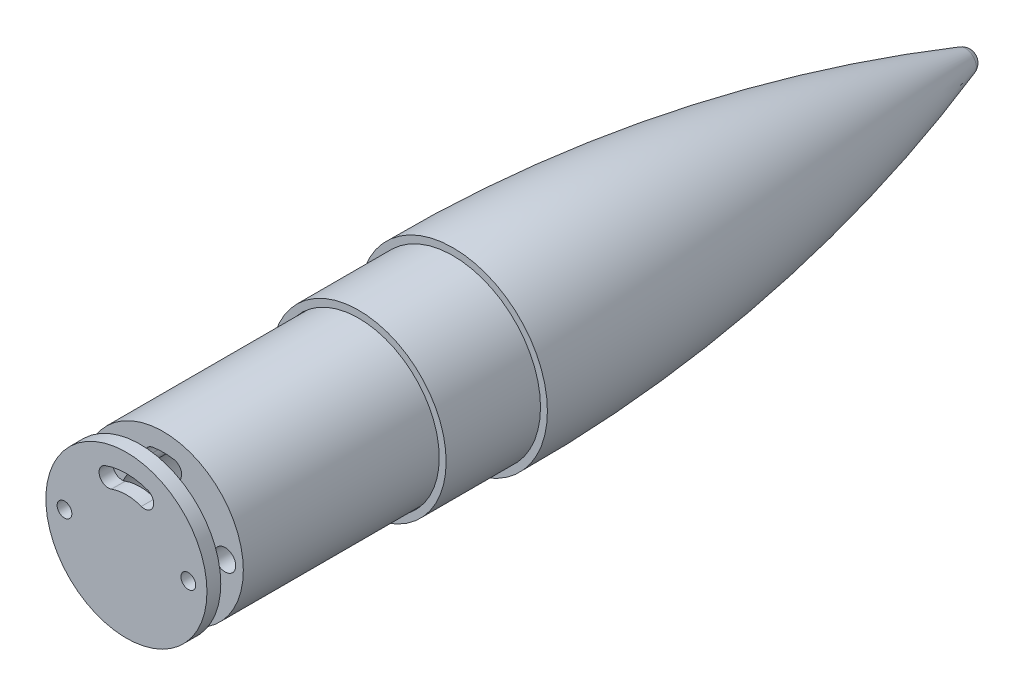
SolidWorks part; units mm, degrees
other "Battery Cover"
other "Battery Bay"
other "Nose Cone"
ref_plane "Front Plane" through (0, 0, 0) normal (0, 0, 1) x (1, 0, 0)
ref_plane "Top Plane" through (0, 0, 0) normal (0, 1, 0) x (1, 0, 0)
ref_plane "Right Plane" through (0, 0, 0) normal (1, 0, 0) x (0, 0, -1)
sketch "Sketch1" plane through (0, 0, 0) normal (0, 1, 0) x (1, 0, 0)
  line L0 (0, 0) -> (0, 110) construction
  line L1 (0, 0) -> (19, 0) construction
  line L2 (19, 0) -> (19, -100) construction
  line L3 (0, 110) -> (-1.2375, 110) construction
  line L4 (19, 0) -> (17.5, 0)
  line L5 (17.5, 0) -> (17.5, -22)
  arc A0 (0, 110) -> (0.9469, 109.3215) centre (0, 109) cw
  arc A1 (0.9469, 109.3215) -> (19, 0) centre (-321.0278, 0) cw
  dimension "D1" = 1
  dimension "D2" = 19
  dimension "D3" = 110
  dimension "D4" = 100
  dimension "D5" = 1.5
  dimension "D7" = 22
revolve "Revolve-Thin1" add sketch "Sketch1" angle 360 about L0 wall 1.5
sketch "Sketch2" plane through (0, 0, 0) normal (0, 1, 0) x (1, 0, 0)
  line L8 (0, 0) -> (0, 45.5852) construction
  line L9 (-17.5, -22) -> (-17.5, 0)
  line L10 (17.5, 0) -> (17.5, -22)
  line L11 (17.5, 0) -> (17.5, -22)
  line L12 (0, 70.542) -> (9.5, 70.542)
  line L13 (9.5, 70.542) -> (9.5, -64.458)
  line L14 (9.5, 70.542) -> (11.5, 70.542) construction
  line L15 (0, 70.542) -> (0, 72.542)
  line L16 (0, 72.542) -> (11.0694, 72.542)
  line L17 (17.4, -64.458) -> (17.4, 31.8988)
  line L18 (9.5, -64.458) -> (17.4, -64.458)
  arc A0 (-0.9469, 109.3215) -> (-19, 0) centre (321.0278, 0) ccw
  arc A1 (19, 0) -> (0.9469, 109.3215) centre (-321.0278, 0) ccw
  arc A3 (19, 0) -> (0.9469, 109.3215) centre (-321.0278, 0) ccw construction
  arc A4 (17.4, 31.8988) -> (11.0694, 72.542) centre (-321.0278, 0) ccw
  arc A5 (18.9, 0) -> (0.8522, 109.2894) centre (-321.0278, 0) ccw construction
  point P20 (17.4, 31.8512)
  dimension "D6" = 2
  dimension "D2" = 0.1
  dimension "D1" = 9.5
  dimension "D4" = 0.1
  dimension "D5" = 135
  dimension "D3" = 2
revolve "Revolve2" add sketch "Sketch2" angle 360 about L8 region at (13.0616, 0, 0.9729)
sketch "Sketch4" plane through (0, 0, 0) normal (1, 0, 0) x (0, 0, -1)
  line L0 (-64.458, 9.5) -> (70.542, 9.5)
  line L1 (71.0223, -9.5) -> (-58.9777, -9.5)
  line L2 (70.542, 9.5) -> (50.542, 13.5)
  line L3 (-64.458, 9.5) -> (70.542, 9.5)
  line L4 (50.542, 13.5) -> (-64.458, 13.5)
  line L5 (-64.458, 13.5) -> (-64.458, 9.5)
  line L6 (70.542, 9.5) -> (-64.458, 9.5)
  line L7 (-39.5923, 0) -> (23.8304, 0) construction
  line L8 (-64.458, 17.4) -> (-64.458, -17.4) construction
  line L9 (70.542, 9.5) -> (70.542, -9.5) construction
  point P7 (-64.5166, 9.5)
  point P13 (-58.9777, 13.5)
  point P14 (77.3799, 9.5)
  point P16 (50.2505, 9.5)
  point P17 (64.1365, 9.5)
  point P18 (0, 0)
  dimension "D1" = 4
  dimension "D2" = 20
revolve "Cut-Revolve2" cut sketch "Sketch4" angle 20 about L7 region at (0, 11.4467, 1.8247) other way angle 20
fillet "Fillet1" radius 2 4 edges at (3.2492, 8.9271, -3.042) (-3.2492, 8.9271, -3.042) (4.6173, 12.6859, 6.958) (-4.6173, 12.6859, 6.958)
sketch "Sketch5" plane through (0, 0, 64.458) normal (0, 0, 1) x (1, 0, 0)
  line L0 (-13.45, 0) -> (13.45, 0) construction
  line L1 (-17.4, 0) -> (-9.5, 0) construction
  circle A0 centre (-13.45, 0) radius 2.3
  circle A1 centre (13.45, 0) radius 2.3
  circle A2 centre (0, 0) radius 17.4 construction
  arc A3 (-4.7522, 8.226) -> (4.7522, 8.226) centre (0, 0) ccw construction
  point P4 (0, 0)
  point P13 (-13.45, 0)
  dimension "D1" = 4.6
extrude "Cut-Extrude2" cut sketch "Sketch5" against normal blind 6
sketch "Sketch6" plane through (0, 0, 64.458) normal (0, 0, 1) x (1, 0, 0)
  circle A0 centre (0, 0) radius 17.5
  circle A3 centre (13.45, 0) radius 1.6
  circle A4 centre (-13.45, 0) radius 1.6
  arc A5 (-3.9405, 10.8038) -> (3.926, 10.8091) centre (0, 0) cw construction
  arc A6 (4.6088, 12.6889) -> (-4.6258, 12.6828) centre (0, 0) ccw
  arc A7 (3.2432, 8.9293) -> (-3.2552, 8.9249) centre (0, 0) ccw
  arc A8 (3.2432, 8.9293) -> (4.6088, 12.6889) centre (3.926, 10.8091) ccw
  arc A9 (-4.6258, 12.6828) -> (-3.2552, 8.9249) centre (-3.9405, 10.8038) ccw
  arc A10 (-4.7522, 8.226) -> (4.7522, 8.226) centre (0, 0) ccw construction
  arc A11 (2.3407, 13.2955) -> (-2.3407, 13.2955) centre (0, 0) ccw construction
  arc A12 (-4.7522, 8.226) -> (-3.8733, 10.6418) centre (-5.7527, 9.9577) ccw construction
  arc A13 (-4.7522, 8.226) -> (-3.8733, 10.6418) centre (-5.7527, 9.9577) ccw construction
  arc A14 (3.8733, 10.6418) -> (2.3407, 13.2955) centre (1.9939, 11.3258) ccw construction
  circle A15 centre (0, 0) radius 17.5 construction
  point P4 (13.45, 0)
  point P6 (-11.15, -6.3645)
  point P12 (-0.0077, 11.5)
  point P17 (0, 0)
  point P24 (-3.8733, 10.6418)
  point P31 (3.8733, 10.6418)
  point P33 (3.926, 10.8091)
  point P39 (-13.45, 0)
  dimension "D1" = 3.2
extrude "Boss-Extrude1" add sketch "Sketch6" along normal blind 3 from offset 5 separate body
